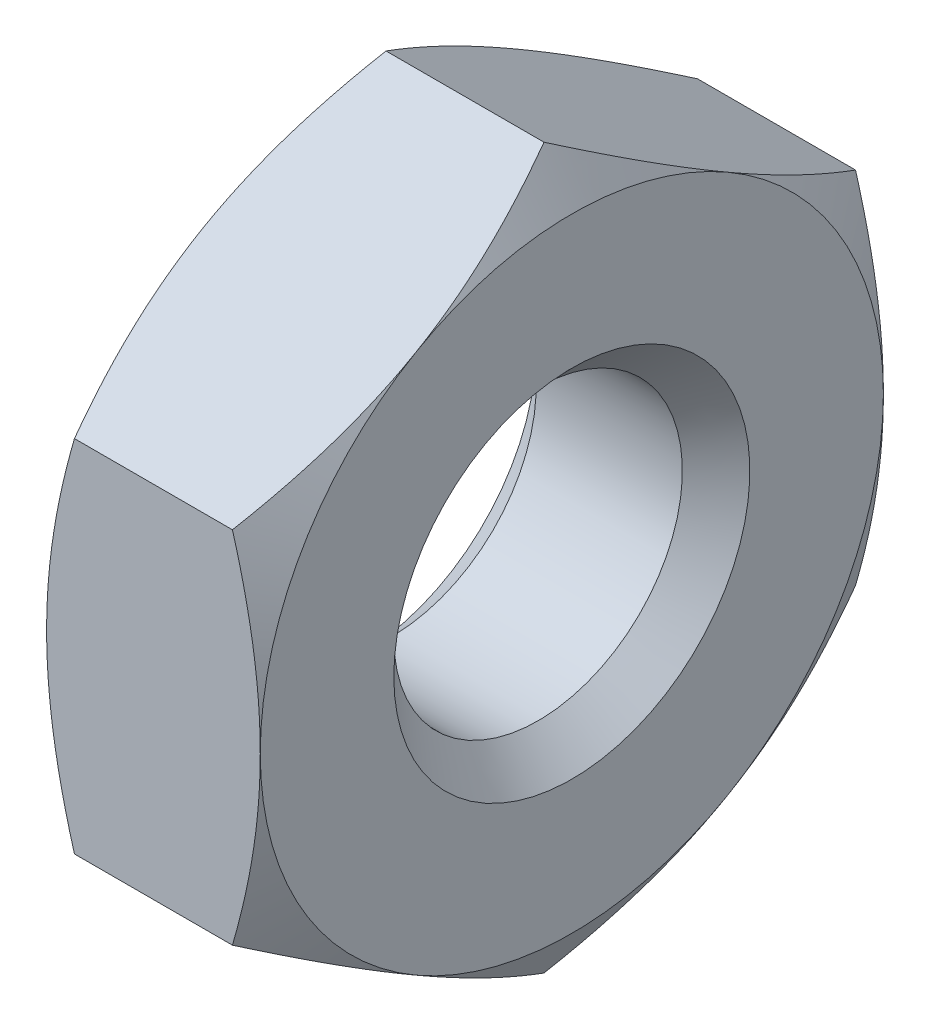
SolidWorks part; units mm, degrees
ref_plane "前视基准面" through (0, 0, 0) normal (0, 0, 1) x (1, 0, 0)
ref_plane "上视基准面" through (0, 0, 0) normal (0, 1, 0) x (1, 0, 0)
ref_plane "右视基准面" through (0, 0, 0) normal (1, 0, 0) x (0, 0, -1)
sketch "草图1" plane through (0, 0, 0) normal (0, 0, 1) x (1, 0, 0)
  line L0 (-1.2, 0) -> (-1.2, 3.5)
  line L1 (-1.2, 3.5) -> (-0.7959, 4.2)
  line L2 (-0.7959, 4.2) -> (0.7959, 4.2)
  line L3 (0.7959, 4.2) -> (1.2, 3.5)
  line L4 (1.2, 3.5) -> (1.2, 0)
  line L5 (1.2, 0) -> (-1.2, 0)
  line L6 (1.2, 0) -> (-1.2, 0) construction
revolve "旋转1" add sketch "草图1" angle 360 about L6 reverse direction yes
sketch "草图2" plane through (0, 0, 0) normal (1, 0, 0) x (0, 0, -1)
  line L0 (-8.1, -8.1) -> (8.1, -8.1)
  line L1 (8.1, -8.1) -> (8.1, 8.1)
  line L2 (8.1, 8.1) -> (-8.1, 8.1)
  line L3 (-8.1, 8.1) -> (-8.1, -8.1)
  line L4 (-3.5, 2.0207) -> (-3.5, -2.0207)
  line L5 (-3.5, -2.0207) -> (0, -4.0415)
  line L6 (0, -4.0415) -> (3.5, -2.0207)
  line L7 (3.5, -2.0207) -> (3.5, 2.0207)
  line L8 (3.5, 2.0207) -> (0, 4.0415)
  line L9 (0, 4.0415) -> (-3.5, 2.0207)
extrude "切除-拉伸1" cut sketch "草图2" along normal blind 2.4 and the other way blind 2.4
sketch "草图3" plane through (0, 0, 0) normal (0, 0, 1) x (1, 0, 0)
  line L0 (-1.2, 0) -> (-1.2, 2)
  line L1 (-1.2, 2) -> (-0.821, 1.621)
  line L2 (-0.821, 1.621) -> (0.821, 1.621)
  line L3 (0.821, 1.621) -> (1.2, 2)
  line L4 (1.2, 2) -> (1.2, 0)
  line L5 (1.2, 0) -> (-1.2, 0)
  line L6 (1.2, 0) -> (-1.2, 0) construction
revolve "切除-旋转1" cut sketch "草图3" angle 360 about L6 reverse direction yes
cosmetic thread "装饰螺纹线1" parameters "D1"=2.021, "D2"=4
ref_plane "n_b XY" through (0, 0, 0) normal (1, 0, 0) x (0, 0, -1)
ref_plane "n_b XZ" through (0, 0, 0) normal (0, -1, 0) x (1, 0, 0)
ref_plane "n_b YZ" through (0, 0, 0) normal (0, 0, -1) x (-1, 0, 0)
ref_axis "n_b X" through (0, 0, 80.9) along (0, 0, -1)
ref_axis "n_b Y" through (0, -50, 0) along (0, 1, 0)
ref_axis "n_b Z" through (80.9, 0, 0) along (-1, 0, 0)
sketch3d "n_b"
  point P0 (0, 0, 0)
